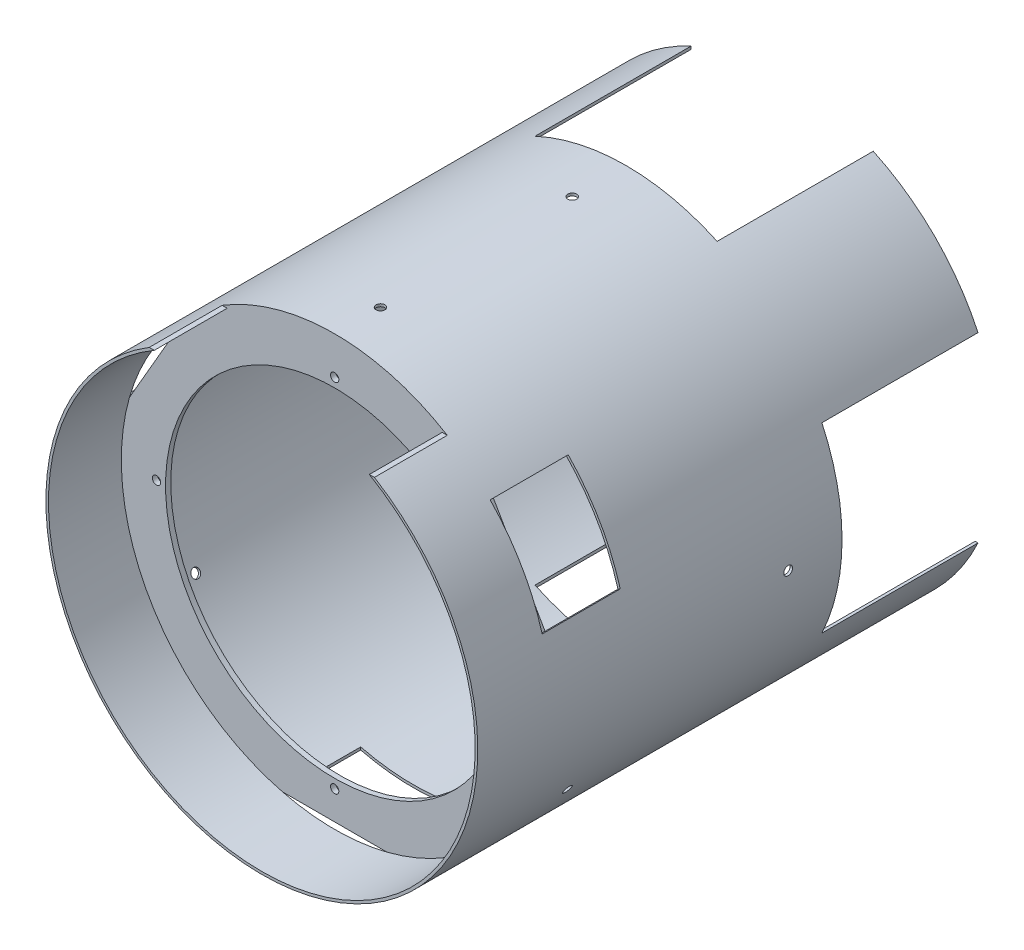
SolidWorks part; units mm, degrees
material "ABS"
ref_plane "前视基准面" through (0, 0, 0) normal (0, 0, 1) x (1, 0, 0)
ref_plane "上视基准面" through (0, 0, 0) normal (0, 1, 0) x (1, 0, 0)
ref_plane "右视基准面" through (0, 0, 0) normal (1, 0, 0) x (0, 0, -1)
sketch "草图1" plane through (0, 0, 0) normal (0, 0, 1) x (1, 0, 0)
  circle A0 centre (0, 0) radius 83
  dimension "D1" = 166
extrude "凸台-拉伸1" add sketch "草图1" along normal blind 100 and the other way blind 100
shell "抽壳1" thickness 1 removed face at (83, 0, -100) removed face at (83, 0, 100)
ref_plane "基准面1" through (0, 0, 70) normal (0, 0, 1) x (1, 0, 0)
sketch "草图2" plane through (0, 0, 70) normal (0, 0, 1) x (1, 0, 0)
  circle A0 centre (0, 0) radius 82.5
  circle A1 centre (0, 0) radius 65
  dimension "D1" = 165
  dimension "D2" = 130
extrude "凸台-拉伸2" add sketch "草图2" along normal blind 2
sketch "草图3" plane through (0, 0, 100) normal (0, 0, 1) x (1, 0, 0)
  line L0 (0, 0) -> (0, 116.4423) construction
  line L1 (43.2734, 70.8267) -> (-43.2734, 70.8267)
  circle A0 centre (0, 0) radius 83 construction
  arc A1 (43.2734, 70.8267) -> (-43.2734, 70.8267) centre (0, 0) ccw
  point P10 (0, 70.8267)
extrude "切除-拉伸1" cut sketch "草图3" against normal up to surface (28 mm away) up to face at (65, 0, 72)
sketch "草图5" plane through (0, 0, 0) normal (0, 1, 0) x (1, 0, 0)
  line L0 (0, 0) -> (0, 70) construction
  line L1 (35, 40) -> (-35, 40)
  line L2 (35, 40) -> (35, 100)
  line L3 (35, 100) -> (-35, 100)
  line L4 (-35, 40) -> (-35, 100)
  line L5 (35, 40) -> (-35, 100) construction
  line L6 (35, 100) -> (-35, 40) construction
  point P0 (0, 70)
  dimension "D1" = 60
  dimension "D2" = 40
  dimension "D3" = 70
extrude "切除-拉伸2" cut sketch "草图5" against normal through all and the other way through all
pattern_circular "阵列(圆周)1" count 4 over 360 about axis through (0, 0, -100) along (0, 0, 1) of "切除-拉伸2"
sketch "草图6" plane through (0, 0, 72) normal (0, 0, -1) x (1, 0, 0)
  line L0 (20, 84.5) -> (-20, 84.5)
  line L1 (-83.1791, -24.9295) -> (-63.1791, -59.5705)
  line L2 (-83.1791, -24.9295) -> (-78.849, -22.4295)
  line L3 (-78.849, -22.4295) -> (-58.849, -57.0705)
  line L4 (-63.1791, -59.5705) -> (-58.849, -57.0705)
  line L5 (-83.1791, -24.9295) -> (-58.849, -57.0705) construction
  line L6 (-78.849, -22.4295) -> (-63.1791, -59.5705) construction
  line L7 (20, 84.5) -> (20, 79.5)
  line L8 (20, 79.5) -> (-20, 79.5)
  line L9 (-20, 84.5) -> (-20, 79.5)
  line L10 (20, 84.5) -> (-20, 79.5) construction
  line L11 (20, 79.5) -> (-20, 84.5) construction
  line L12 (63.1791, -59.5705) -> (83.1791, -24.9295)
  line L13 (63.1791, -59.5705) -> (58.849, -57.0705)
  line L14 (58.849, -57.0705) -> (78.849, -22.4295)
  line L15 (83.1791, -24.9295) -> (78.849, -22.4295)
  line L16 (63.1791, -59.5705) -> (78.849, -22.4295) construction
  line L17 (58.849, -57.0705) -> (83.1791, -24.9295) construction
  line L18 (-71.0141, -41) -> (0, 0) construction
  line L19 (0, 0) -> (0, -99.515) construction
  arc A1 (41.3229, -70.8267) -> (-41.3229, -70.8267) centre (0, 0) ccw construction
  point P0 (-71.0141, -41)
  point P11 (0, 82)
  point P16 (71.0141, -41)
  point P22 (0, 0)
  point P23 (0, 0)
  point P24 (-63.722, -55.305)
  point P25 (-63.0012, -60.2115)
  dimension "D1" = 40
  dimension "D2" = 5
  dimension "D4" = 60
  dimension "D3" = 3
extrude "切除-拉伸3" cut sketch "草图6" along normal blind 30
sketch "草图7" plane through (0, 0, 72) normal (0, 0, 1) x (1, 0, 0)
  line L0 (0, 0) -> (0, -68.5) construction
  line L1 (0, 0) -> (68.5, 0) construction
  line L2 (0, 0) -> (-68.5, 0) construction
  line L3 (0, 68.5) -> (0, 0) construction
  circle A0 centre (0, 68.5) radius 1.6
  circle A1 centre (-68.5, 0) radius 1.6
  circle A2 centre (0, -68.5) radius 1.6
  circle A3 centre (68.5, 0) radius 1.6
  circle A4 centre (0, 0) radius 68.5 construction
  dimension "D1" = 137
  dimension "D2" = 3.2
  dimension "D3" = 3.2
  dimension "D4" = 3.2
  dimension "D5" = 3.2
extrude "切除-拉伸4" cut sketch "草图7" against normal up to next
sketch "草图8" plane through (0, 0, 0) normal (0, 1, 0) x (1, 0, 0)
  line L0 (20, -72) -> (20, -42) construction
  line L1 (-20, -42) -> (20, -42) construction
  circle A0 centre (0, -54.4) radius 1.7
  dimension "D1" = 3.4
  dimension "D2" = 20
  dimension "D3" = 12.4
extrude "切除-拉伸5" cut sketch "草图8" along normal through all
pattern_circular "阵列(圆周)2" count 3 every 120 about axis through (0, 0, 72) along (0, 0, -1) of "切除-拉伸5"
sketch "草图9" plane through (0, 0, 0) normal (0, 1, 0) x (1, 0, 0)
  line L0 (0, 19.3) -> (0, 0) construction
  line L1 (35, 40) -> (-35, 40) construction
  circle A1 centre (0, 19.3) radius 1.7
  dimension "D2" = 3.4
  dimension "D1" = 20.7
extrude "切除-拉伸6" cut sketch "草图9" along normal through all
pattern_circular "阵列(圆周)3" count 4 every 90 about axis through (0, 0, -40) along (0, 0, -1) of "切除-拉伸6"
